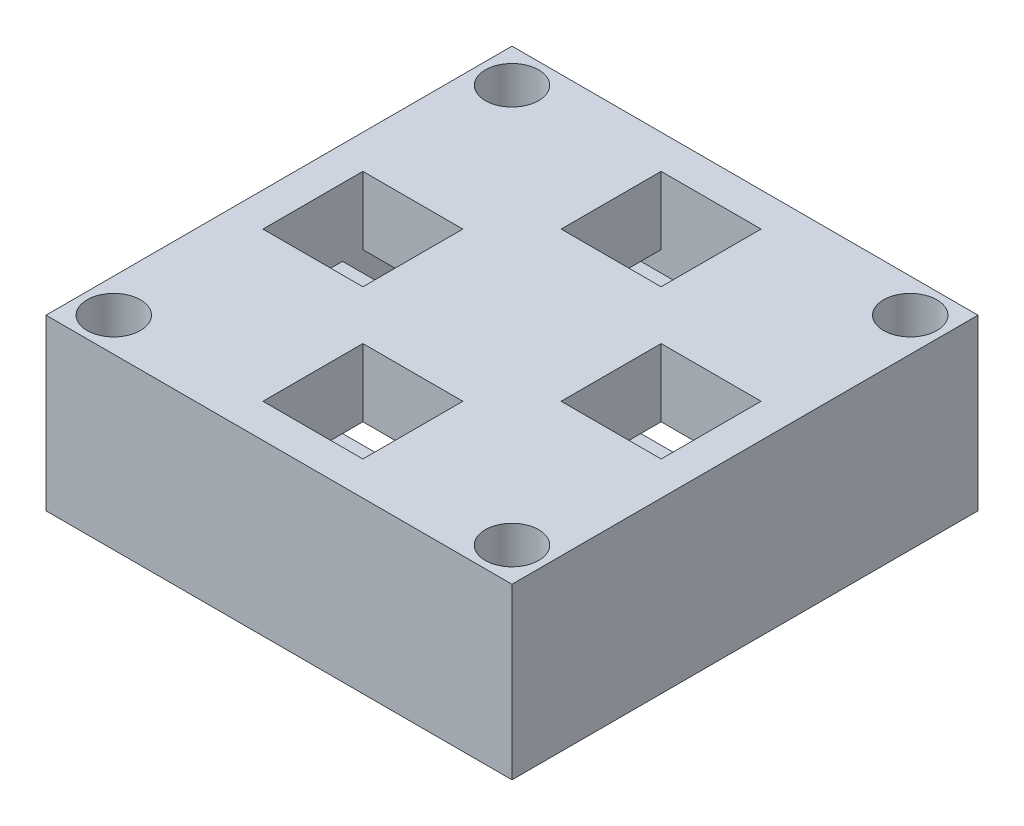
SolidWorks part; units mm, degrees
ref_plane "Front Plane" through (0, 0, 0) normal (0, 0, 1) x (1, 0, 0)
ref_plane "Top Plane" through (0, 0, 0) normal (0, 1, 0) x (1, 0, 0)
ref_plane "Right Plane" through (0, 0, 0) normal (1, 0, 0) x (0, 0, -1)
sketch "Sketch1" plane through (0, 0, 0) normal (0, 1, 0) x (1, 0, 0)
  line L1 (-27.5, 27.5) -> (27.5, 27.5)
  line L2 (-27.5, 27.5) -> (-27.5, -27.5)
  line L3 (-27.5, -27.5) -> (27.5, -27.5)
  line L4 (27.5, 27.5) -> (27.5, -27.5)
  line L5 (-27.5, 27.5) -> (27.5, -27.5) construction
  line L6 (-27.5, -27.5) -> (27.5, 27.5) construction
  line L7 (-5.9, 23.5) -> (5.9, 23.5)
  line L8 (-5.9, 23.5) -> (-5.9, 11.7)
  line L9 (-5.9, 11.7) -> (5.9, 11.7)
  line L10 (5.9, 23.5) -> (5.9, 11.7)
  line L11 (-5.9, 23.5) -> (5.9, 11.7) construction
  line L12 (-5.9, 11.7) -> (5.9, 23.5) construction
  line L13 (11.7, 5.9) -> (23.5, 5.9)
  line L14 (11.7, 5.9) -> (11.7, -5.9)
  line L15 (11.7, -5.9) -> (23.5, -5.9)
  line L16 (23.5, 5.9) -> (23.5, -5.9)
  line L17 (11.7, 5.9) -> (23.5, -5.9) construction
  line L18 (11.7, -5.9) -> (23.5, 5.9) construction
  line L19 (-23.5, 5.9) -> (-11.7, 5.9)
  line L20 (-23.5, 5.9) -> (-23.5, -5.9)
  line L21 (-23.5, -5.9) -> (-11.7, -5.9)
  line L22 (-11.7, 5.9) -> (-11.7, -5.9)
  line L23 (-23.5, 5.9) -> (-11.7, -5.9) construction
  line L24 (-23.5, -5.9) -> (-11.7, 5.9) construction
  line L25 (5.9, -23.5) -> (-5.9, -23.5)
  line L26 (5.9, -23.5) -> (5.9, -11.7)
  line L27 (5.9, -11.7) -> (-5.9, -11.7)
  line L28 (-5.9, -23.5) -> (-5.9, -11.7)
  line L29 (5.9, -23.5) -> (-5.9, -11.7) construction
  line L30 (5.9, -11.7) -> (-5.9, -23.5) construction
  point P0 (0, 0)
  point P6 (0, 17.6)
  point P11 (17.6, 0)
  point P16 (-17.6, 0)
  point P21 (0, -17.6)
  dimension "D1" = 55
  dimension "D2" = 55
  dimension "D3" = 11.8
  dimension "D4" = 11.8
  dimension "D5" = 11.8
  dimension "D6" = 11.8
  dimension "D7" = 11.8
  dimension "D8" = 11.8
  dimension "D9" = 11.8
  dimension "D10" = 11.8
  dimension "D11" = 4
  dimension "D12" = 4
  dimension "D13" = 4
  dimension "D14" = 4
  dimension "D15" = 27.5
  dimension "D16" = 27.5
  dimension "D17" = 27.5
extrude "Boss-Extrude1" add sketch "Sketch1" along normal blind 8
sketch "Sketch2" plane through (0, 0, 0) normal (0, -1, 0) x (1, 0, 0)
  line L0 (-5.9, 23.5) -> (-23.5, 23.5)
  line L1 (-11.8, 21.1) -> (11.8, 21.1)
  line L2 (-11.8, 21.1) -> (-11.8, 14.1)
  line L3 (-11.8, 14.1) -> (11.8, 14.1)
  line L4 (11.8, 21.1) -> (11.8, 14.1)
  line L5 (-11.8, 21.1) -> (11.8, 14.1) construction
  line L6 (-11.8, 14.1) -> (11.8, 21.1) construction
  line L12 (-23.5, 3.5) -> (23.5, 3.5)
  line L17 (-23.5, 3.5) -> (-23.5, -3.5)
  line L18 (-23.5, -3.5) -> (23.5, -3.5)
  line L19 (-11.8, -14.1) -> (11.8, -14.1)
  line L20 (-11.8, -14.1) -> (-11.8, -21.1)
  line L21 (-11.8, -21.1) -> (11.8, -21.1)
  line L22 (11.8, -14.1) -> (11.8, -21.1)
  line L23 (-11.8, -14.1) -> (11.8, -21.1) construction
  line L24 (-11.8, -21.1) -> (11.8, -14.1) construction
  line L25 (-23.5, -23.5) -> (-23.5, 23.5)
  line L26 (23.5, -23.5) -> (-23.5, -23.5)
  line L27 (-5.9, 23.5) -> (23.5, 23.5)
  line L28 (23.5, -23.5) -> (23.5, 23.5)
  line L31 (-5.9, 11.7) -> (-5.9, 23.5) construction
  line L32 (5.9, 11.7) -> (-5.9, 11.7) construction
  line L33 (-5.9, -23.5) -> (-5.9, -11.7) construction
  line L36 (23.5, 3.5) -> (23.5, -3.5)
  line L37 (-23.5, 3.5) -> (23.5, -3.5) construction
  line L38 (-23.5, -3.5) -> (23.5, 3.5) construction
  point P0 (0, 17.6)
  point P5 (-15.2275, 0.8547)
  point P6 (0, 0)
  point P10 (14.3332, 1.7102)
  point P15 (0, -17.6)
  point P40 (-5.9, -17.6)
  line M21 (-23.5, -5.9) -> (-23.5, 5.9)
  line M24 (5.9, -23.5) -> (-5.9, -23.5)
  line M27 (27.5, -27.5) -> (27.5, 27.5)
  line M28 (27.5, 27.5) -> (-27.5, 27.5)
  line M29 (-27.5, 27.5) -> (-27.5, -27.5)
  line M30 (-27.5, -27.5) -> (27.5, -27.5)
  line M31 (23.5, 5.9) -> (23.5, -5.9)
  line M36 (-5.9, 23.5) -> (5.9, 23.5)
  dimension "D1" = 23.6
  dimension "D2" = 7
  dimension "D1*(1/4)" = 5.8004
  dimension "D3" = 2.4
  dimension "D1/4" = 5.9
  dimension "D4" = 7
  dimension "D5" = 2.4
  dimension "D6" = 5.9
  dimension "D7" = 7
  dimension "D8" = 0
extrude "Boss-Extrude7" add sketch "Sketch2" along normal blind 12 contours L28 L26 L25 L0 L27 M30 M27 M28 M29 M24 M21 M36 M31 region at (0, 0, -26.7222)
extrude "Boss-Extrude8" add sketch "Sketch2<5>" along normal blind 8 contours L1 L4 L3 L2 | L12 L36 L18 L17 | L19 L22 L21 L20
sketch "Sketch2<5>" plane through (0, 0, 0) normal (0, -1, 0) x (1, 0, 0) same geometry as "Sketch2"
sketch "Sketch6" plane through (0, -12, 0) normal (0, -1, 0) x (1, 0, 0)
  circle A0 centre (-23.5, 23.5) radius 3.15
  circle A1 centre (23.5, 23.5) radius 3.15
  circle A2 centre (-23.5, -23.5) radius 3.15
  circle A3 centre (23.5, -23.5) radius 3.15
  dimension "D1" = 6.3
extrude "Cut-Extrude1" cut sketch "Sketch6" against normal through all
